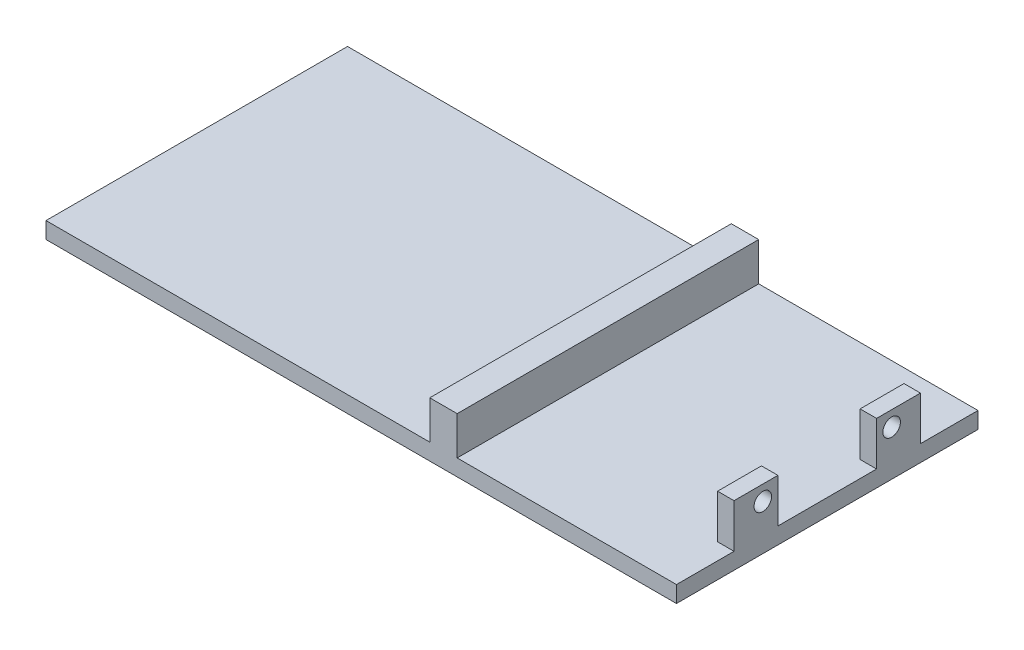
SolidWorks part; units mm, degrees
material "ABS"
ref_plane "Front Plane" through (0, 0, 0) normal (0, 0, 1) x (1, 0, 0)
ref_plane "Top Plane" through (0, 0, 0) normal (0, 1, 0) x (1, 0, 0)
ref_plane "Right Plane" through (0, 0, 0) normal (1, 0, 0) x (0, 0, -1)
sketch "Sketch2" plane through (0, 0, 0) normal (0, 1, 0) x (1, 0, 0)
  line L1 (-30.5455, 36.5455) -> (39.4545, 36.5455)
  line L2 (-30.5455, 36.5455) -> (-30.5455, -18.4545)
  line L3 (-30.5455, -18.4545) -> (39.4545, -18.4545)
  line L4 (39.4545, 36.5455) -> (39.4545, -18.4545)
  line L5 (39.4545, 36.5455) -> (44.4545, 36.5455)
  line L6 (39.4545, 36.5455) -> (39.4545, -18.4545)
  line L7 (39.4545, -18.4545) -> (44.4545, -18.4545)
  line L8 (44.4545, 36.5455) -> (44.4545, -18.4545)
  dimension "D1" = 70
  dimension "D2" = 55
  dimension "D3" = 5
sketch "Sketch5" plane through (0, 0, 0) normal (0, 1, 0) x (1, 0, 0)
  line L1 (39.4545, 36.5455) -> (44.4545, 36.5455)
  line L2 (39.4545, 36.5455) -> (39.4545, -18.4545)
  line L3 (39.4545, -18.4545) -> (44.4545, -18.4545)
  line L4 (44.4545, 36.5455) -> (44.4545, -18.4545)
extrude "Boss-Extrude3" add sketch "Sketch2" along normal blind 3 contours L4 L1 L2 L3 region at (4.4545, 0, -9.0455)
extrude "Boss-Extrude4" add sketch "Sketch5" along normal blind 10
sketch "Sketch6" plane through (0, 0, 0) normal (0, 1, 0) x (1, 0, 0)
  line L1 (44.4545, 36.5455) -> (84.4545, 36.5455)
  line L2 (44.4545, 36.5455) -> (44.4545, -18.4545)
  line L3 (44.4545, -18.4545) -> (84.4545, -18.4545)
  line L4 (84.4545, 36.5455) -> (84.4545, -18.4545)
  dimension "D1" = 40
extrude "Boss-Extrude5" add sketch "Sketch6" along normal blind 3
sketch "Sketch8" plane through (0, 0, 0) normal (0, 1, 0) x (1, 0, 0)
  line L0 (84.4545, -18.4545) -> (84.4545, 36.5455) construction
  line L1 (84.4545, 26.0455) -> (81.4545, 26.0455)
  line L2 (84.4545, 26.0455) -> (84.4545, 18.0455)
  line L3 (84.4545, 18.0455) -> (81.4545, 18.0455)
  line L4 (81.4545, 26.0455) -> (81.4545, 18.0455)
  line L5 (44.4545, -18.4545) -> (84.4545, -18.4545) construction
  line L6 (84.4545, 0.0455) -> (81.4545, 0.0455)
  line L7 (84.4545, 0.0455) -> (84.4545, -7.9545)
  line L8 (84.4545, -7.9545) -> (81.4545, -7.9545)
  line L9 (81.4545, 0.0455) -> (81.4545, -7.9545)
  dimension "D1" = 8
  dimension "D2" = 8
  dimension "D3" = 18
  dimension "D4" = 10.5
  dimension "D5" = 3
  dimension "D6" = 3
extrude "Boss-Extrude6" add sketch "Sketch8" along normal blind 11
sketch "Sketch9" plane through (84.4545, 0, 0) normal (1, 0, 0) x (0, 0, -1)
  line L0 (0.0455, 11) -> (0.0455, 3) construction
  line L1 (-7.9545, 11) -> (0.0455, 11) construction
  line L2 (18.0455, 11) -> (18.0455, 3) construction
  line L3 (18.0455, 11) -> (26.0455, 11) construction
  circle A0 centre (-2.7045, 8.25) radius 1.6
  circle A1 centre (20.7955, 8.25) radius 1.6
  dimension "D1" = 2.75
  dimension "D3" = 2.75
  dimension "D2" = 2.75
  dimension "D4" = 2.75
extrude "Cut-Extrude1" cut sketch "Sketch9" against normal blind 11
